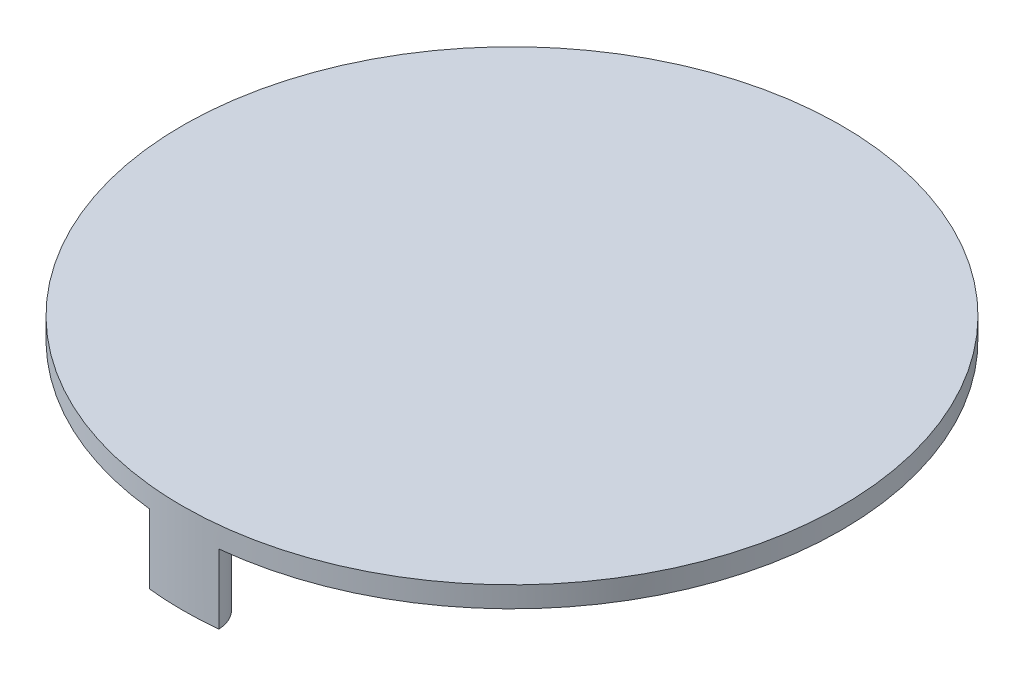
SolidWorks part; units mm, degrees
ref_plane "Front Plane" through (0, 0, 0) normal (0, 0, 1) x (1, 0, 0)
ref_plane "Top Plane" through (0, 0, 0) normal (0, 1, 0) x (1, 0, 0)
ref_plane "Right Plane" through (0, 0, 0) normal (1, 0, 0) x (0, 0, -1)
sketch "Sketch2" plane through (0, 0, 0) normal (0, 1, 0) x (1, 0, 0)
  circle A0 centre (0, 0) radius 47.5
  dimension "D1" = 95
extrude "Boss-Extrude1" add sketch "Sketch2" along normal blind 3
sketch "Sketch4" plane through (0, 0, 0) normal (0, -1, 0) x (1, 0, 0)
  arc A0 (-4.9931, 47.2368) -> (4.9931, 47.2368) centre (0, 47.5) ccw
  circle A1 centre (0, 0) radius 47.5 construction
  circle A3 centre (0, 0) radius 47.5
  arc A4 (4.9931, 47.2368) -> (-4.9931, 47.2368) centre (0, 0) ccw
  point P1 (0, 0)
  dimension "D1" = 10
  dimension "D2" = 0
extrude "Boss-Extrude2" add sketch "Sketch4" along normal blind 10
